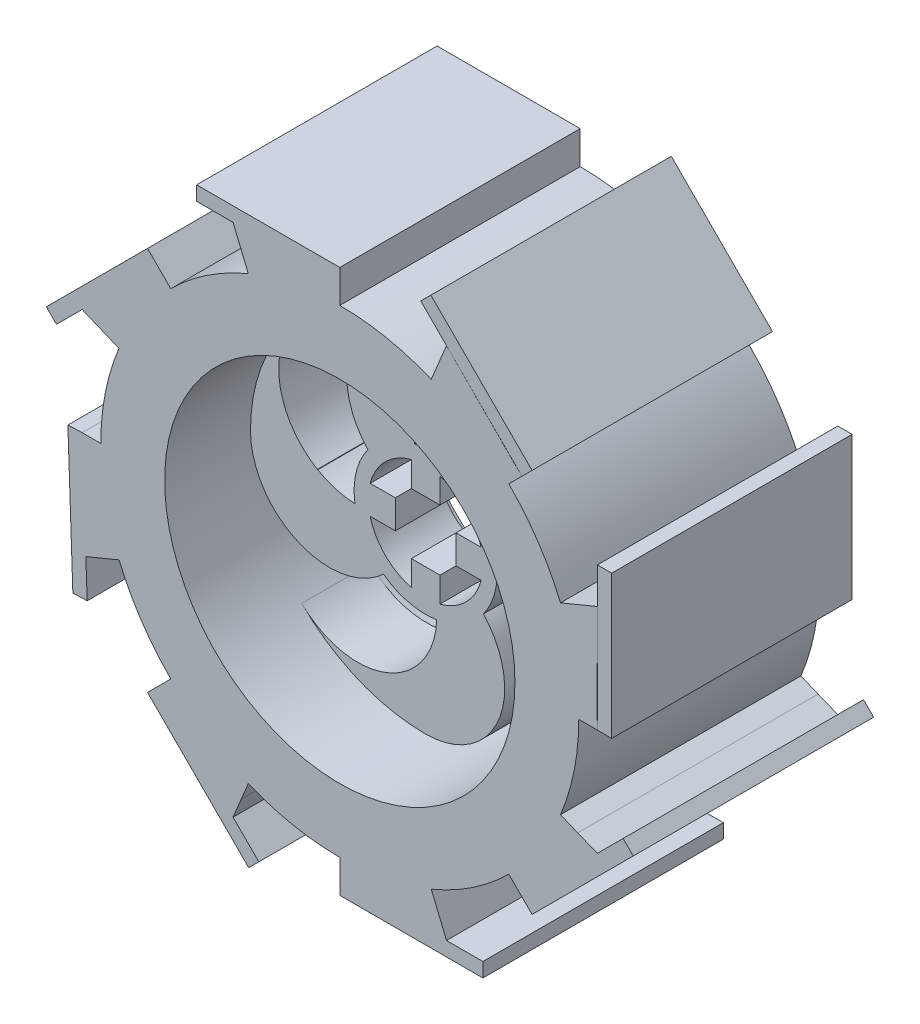
SolidWorks part; units mm, degrees
ref_plane "Front Plane" through (0, 0, 0) normal (0, 0, 1) x (1, 0, 0)
ref_plane "Top Plane" through (0, 0, 0) normal (0, 1, 0) x (1, 0, 0)
ref_plane "Right Plane" through (0, 0, 0) normal (1, 0, 0) x (0, 0, -1)
sketch "Sketch1" plane through (0, 0, 0) normal (0, 0, 1) x (1, 0, 0)
  line L0 (0, 83.5) -> (0, -83.5)
  line L1 (-83.5, 0) -> (83.5, 0)
  line L2 (0, 0) -> (59.0434, 59.0434)
  line L3 (0, 0) -> (-59.0434, 59.0434)
  line L4 (0, 0) -> (-59.0434, -59.0434)
  line L5 (0, 0) -> (63.6396, -63.6396)
  line L6 (0, 0) -> (-31.9541, 77.1439)
  line L7 (0, 0) -> (31.9541, -77.1439)
  line L8 (0, 0) -> (59.0434, -59.0434)
  line L9 (0, 0) -> (34.4523, 83.1447)
  line L10 (-31.9541, -77.1439) -> (0, 0)
  line L11 (-77.1439, -31.9541) -> (0, 0)
  line L12 (0, 0) -> (77.1439, 31.9541)
  line L13 (0, 0) -> (31.9541, 77.1439)
  line L14 (0, 0) -> (-77.1439, 31.9541)
  line L15 (-77.1439, 31.9541) -> (77.1439, -31.9541)
  line L16 (0, 0) -> (0, 90)
  line L17 (0, 0) -> (63.6396, 63.6396)
  line L18 (0, 0) -> (-34.4523, 83.1447)
  line L19 (0, 0) -> (-63.6396, 63.6396)
  line L20 (0, 0) -> (-83.5, 34.5496)
  line L21 (0, 0) -> (-90, 0)
  line L22 (0, 0) -> (-83.111, -34.5335)
  line L23 (0, 0) -> (-83.111, -34.5335)
  line L24 (0, 0) -> (-63.6396, -63.6396)
  line L25 (0, 0) -> (-34.4523, -83.1447)
  line L26 (0, 0) -> (0, -90)
  line L27 (0, 0) -> (34.4523, -83.1447)
  line L28 (0, 0) -> (83.111, -34.5335)
  line L29 (0, 0) -> (90, 0)
  line L30 (0, 0) -> (83.1043, 34.5496)
  circle A0 centre (0, 0) radius 90
  circle A1 centre (0, 0) radius 1.95
  circle A2 centre (0, 0) radius 83.5
  dimension "D1" = 180
  dimension "D2" = 3.9
  dimension "D3" = 167
  dimension "D5" = 45
  dimension "D6" = 22.5
  dimension "D7" = 22.5
extrude "Boss-Extrude1" add sketch "Sketch1" along normal blind 84 contours A2 L16 A0 L18 | A2 L17 A0 L9 | A2 L29 A0 L30 | A2 L5 A0 L28 | A2 L26 A0 L27 | A2 L24 A0 L25 | A2 L21 A0 L22 | A2 L19 A0 L20 | A2 region at (-16.8288, 84.5756, 0) region at (47.9139, 71.6981, 0) region at (-71.7092, 47.8948, 0) region at (16.8288, -84.5756, 0) region at (84.5625, 16.8777, 0) region at (-84.5646, -16.8696, 0) region at (-47.9139, -71.6981, 0) region at (71.677, -47.9505, 0)
sketch "Sketch13" plane through (0, 0, 84) normal (0, 0, 1) x (1, 0, 0)
  line L0 (90, 0) -> (90, 50)
  line L21 (63.6396, 63.6396) -> (28.2843, 98.9949)
  line L22 (0, 90) -> (-50, 90)
  line L23 (-63.6396, 63.6396) -> (-98.9949, 28.2843)
  line L24 (-90, 0) -> (-88.2609, -50)
  line L25 (-63.6396, -63.6396) -> (-28.2843, -98.9949)
  line L26 (0, -90) -> (50, -90)
  line L27 (63.6396, -63.6396) -> (98.9949, -28.2843)
  line L28 (28.2843, 98.9949) -> (63.6396, 63.6396)
  line L29 (28.2843, 98.9949) -> (31.8198, 102.5305)
  line L30 (63.6396, 63.6396) -> (67.1751, 67.1751)
  line L31 (31.8198, 102.5305) -> (67.1751, 67.1751)
  line L32 (0, 90) -> (-50, 90)
  line L33 (0, 90) -> (0, 95)
  line L34 (-50, 90) -> (-50, 95)
  line L35 (0, 95) -> (-50, 95)
  line L36 (-98.9949, 28.2843) -> (-63.6396, 63.6396)
  line L37 (-98.9949, 28.2843) -> (-102.5305, 31.8198)
  line L38 (-63.6396, 63.6396) -> (-67.1751, 67.1751)
  line L39 (-102.5305, 31.8198) -> (-67.1751, 67.1751)
  line L40 (-90, 0) -> (-88.2609, -50)
  line L41 (-90, 0) -> (-95, -0.1739)
  line L42 (-88.2609, -50) -> (-93.2609, -50.1739)
  line L43 (-95, -0.1739) -> (-93.2609, -50.1739)
  line L44 (-63.6396, -63.6396) -> (-28.2843, -98.9949)
  line L45 (-63.6396, -63.6396) -> (-67.1751, -67.1751)
  line L46 (-28.2843, -98.9949) -> (-31.8198, -102.5305)
  line L47 (-67.1751, -67.1751) -> (-31.8198, -102.5305)
  line L48 (0, -90) -> (50, -90)
  line L49 (0, -90) -> (0, -95)
  line L50 (50, -90) -> (50, -95)
  line L51 (0, -95) -> (50, -95)
  line L52 (63.6396, -63.6396) -> (98.9949, -28.2843)
  line L53 (63.6396, -63.6396) -> (67.1751, -67.1751)
  line L54 (98.9949, -28.2843) -> (102.5305, -31.8198)
  line L55 (67.1751, -67.1751) -> (102.5305, -31.8198)
  line L56 (90, 0) -> (90, 50)
  line L57 (90, 0) -> (95, 0)
  line L58 (90, 50) -> (95, 50)
  line L59 (95, 0) -> (95, 50)
  arc A1 (-90, 0) -> (-83.111, -34.5335) centre (0, 0) ccw construction
  arc M26 (-90, 0) -> (-83.111, -34.5335) centre (0, 0) ccw
  dimension "D1" = 50
  dimension "D2" = 50
  dimension "D3" = 50
  dimension "D4" = 50
  dimension "D5" = 50
  dimension "D6" = 50
  dimension "D7" = 50
  dimension "D8" = 50
  dimension "D9" = 5
  dimension "D10" = 5
  dimension "D11" = 5
  dimension "D12" = 5
  dimension "D13" = 5
  dimension "D14" = 5
  dimension "D15" = 5
  dimension "D16" = 5
extrude "Cleats" add sketch "Sketch13" against normal blind 84 contours L39 L37 L23 L38 | L41 L43 L42 L24 M26 | L45 L47 L46 L25 | L49 L51 L50 L26 | L53 L55 L54 L27 | L57 L59 L58 L0 | L31 L29 L21 L30 | L33 L35 L34 L22 region at (92.5, 25, 84) region at (47.7297, 83.085, 84) region at (-25, 92.5, 84) region at (-83.085, 47.7297, 84) region at (-91.632, -25.1069, 84) region at (-47.7297, -83.085, 84) region at (25, -92.5, 84) region at (83.085, -47.7297, 84)
sketch "Sketch14" plane through (0, 0, 0) normal (0, 0, -1) x (-1, 0, 0)
  line L1 (-63.6396, 63.6396) -> (-28.2843, 98.9949) construction
  line L2 (-37.2889, 89.9904) -> (-61.0783, 66.1017)
  line L3 (-61.0783, 66.1017) -> (-34.4523, 83.1447)
  line L5 (0, 90) -> (50, 90) construction
  line L6 (37.2928, 90) -> (0, 90)
  line L7 (0, 90) -> (34.4523, 83.1447)
  line L8 (63.6396, 63.6396) -> (82.9874, 34.8294)
  line L10 (63.6396, 63.6396) -> (98.9949, 28.2843) construction
  line L11 (88.6482, 38.631) -> (63.6396, 63.6396)
  line L12 (83.111, -34.5335) -> (88.7181, -36.8569)
  line L13 (89.7825, -6.253) -> (88.2609, -50) construction
  line L14 (88.7181, -36.8569) -> (90, 0)
  line L15 (90, 0) -> (83.111, -34.5335)
  line L16 (83.1623, 34.4098) -> (90.0284, 37.2508)
  line L18 (63.6396, -63.6396) -> (28.2843, -98.9949) construction
  line L19 (39.2934, -87.9858) -> (63.6396, -63.6396)
  line L20 (63.6396, -63.6396) -> (34.4523, -83.1447)
  line L21 (0, -90) -> (-34.4523, -83.1447)
  line L23 (0, -90) -> (-50, -90) construction
  line L24 (-34.4523, -90) -> (0, -90)
  line L25 (-63.6396, -63.6396) -> (-83.111, -34.5335)
  line L27 (-63.6396, -63.6396) -> (-98.9949, -28.2843) construction
  line L28 (-87.9283, -39.3509) -> (-63.6396, -63.6396)
  line L29 (-90, 0) -> (-83.1043, 34.5496)
  line L30 (90.0284, 37.2508) -> (63.6396, 63.6396)
  line L31 (-90, 0) -> (-90, 50) construction
  line L32 (-90, 34.5496) -> (-89.8887, 0.5574)
  line L35 (-90, 34.5496) -> (-90, 37.4164)
  line L37 (-90, -37.2792) -> (-87.9283, -39.3509)
  line L38 (88.6482, 38.631) -> (90.0284, 37.2508)
  line L39 (37.2928, -89.9864) -> (39.2934, -87.9858)
  line L40 (-37.2928, -90) -> (-34.4523, -90)
  line L43 (37.2928, -89.9864) -> (63.6396, -63.6396)
  line L44 (-37.2928, -90) -> (0, -90)
  line L45 (-90, -37.2792) -> (-63.6396, -63.6396)
  line L46 (-83.111, -34.5335) -> (-90, -37.2792)
  line L47 (-83.1043, 34.5496) -> (-90, 37.4164)
  line L48 (-34.4523, 83.1447) -> (-37.2889, 89.9904)
  line L49 (34.4523, 83.1447) -> (37.3476, 90.132)
  line L50 (34.4523, -83.1447) -> (37.2928, -89.9864)
  line L51 (-34.4523, -83.1447) -> (-37.2928, -90)
  line L52 (-83.111, -34.5335) -> (-90, -37.2792)
  arc M4 (-34.4523, 83.1447) -> (-63.6396, 63.6396) centre (0, 0) ccw
  arc M8 (-83.1043, 34.5496) -> (-90, 0) centre (0, 0) ccw
  arc M12 (-83.111, -34.5335) -> (-63.6396, -63.6396) centre (0, 0) ccw
  arc M16 (-34.4523, -83.1447) -> (0, -90) centre (0, 0) ccw
  arc M20 (34.4523, -83.1447) -> (63.6396, -63.6396) centre (0, 0) ccw
  arc M24 (83.111, -34.5335) -> (89.7825, -6.253) centre (0, 0) ccw
  line M25 (89.7825, -6.253) -> (88.2609, -50)
  arc M32 (83.1623, 34.4098) -> (63.6396, 63.6396) centre (0, 0) ccw
  arc M36 (34.4523, 83.1447) -> (0, 90) centre (0, 0) ccw
extrude "cleats_2" add sketch "Sketch14" against normal blind 84 contours L47 L35 L32 M8 | L48 L2 M4 | L49 L6 M36 | L16 L30 L11 M32 | L12 M24 M25 | L50 L39 L19 M20 | L51 L40 L24 M16 | L46 L37 L28 M12 region at (42.967, 81.3466, 0) region at (-26.9658, 87.9305, 0) region at (-81.2548, 43.094, 0) region at (-87.31, -27.8014, 0) region at (-43.1249, -81.2314, 0) region at (26.9658, -87.9305, 0) region at (81.2206, -43.1487, 0) region at (87.8792, 27.3093, 0)
sketch "Sketch15" plane through (0, 0, 84) normal (0, 0, 1) x (1, 0, 0)
  circle A0 centre (0, 0) radius 61.2
  circle A1 centre (0, 0) radius 20
  dimension "D1" = 122.4
  dimension "D2" = 40
extrude "Middle_cut" cut sketch "Sketch15" against normal blind 84
sketch "Sketch17" plane through (0, 0, 0) normal (0, 0, -1) x (-1, 0, 0)
  line L0 (0, 0) -> (0, 95)
  line L1 (0, 0) -> (67.1751, 67.1751)
  line L2 (0, 0) -> (95, -0.1739)
  line L3 (0, 0) -> (67.1751, -67.1751)
  line L4 (0, 0) -> (0, -95)
  line L5 (0, 0) -> (-67.1751, -67.1751)
  line L6 (0, 0) -> (-95, 0)
  line L7 (0, 0) -> (-67.1751, 67.1751)
  circle A0 centre (0, 0) radius 61.2
  circle A1 centre (0, 33.5876) radius 27.6124
  circle A3 centre (23.75, 23.75) radius 27.6124
  circle A4 centre (33.5876, 0) radius 27.6126
  circle A5 centre (23.75, -23.75) radius 27.6124
  circle A6 centre (0, -33.5876) radius 27.6124
  circle A7 centre (-23.75, -23.75) radius 27.6124
  circle A8 centre (-33.5876, 0) radius 27.6124
  circle A9 centre (-23.75, 23.75) radius 27.6124
  circle M2 centre (0, 0) radius 20
extrude "Boss-Extrude13" add sketch "Sketch17" against normal blind 84 contours A8 A9 A7 A1 M2 | A9 A8 L6 | L6 A8 A7 | L7 A1 M2 | A8 L7 M2 | A8 A6 A7 A5 M2 | A7 A6 L4 | L4 A6 A5 | A6 L5 M2 | L5 A8 M2 | A5 A4 L2 | A6 L3 A4 A5 L2 A3 M2 | L3 A6 M2 | A4 A6 L3 M2 | A5 L2 A0 A4 A3 | A9 A4 A1 A3 M2 | A1 A4 L1 M2 | A1 L1 M2 | A3 A1 L0 | A9 L0 A1 | A9 A1 A0 | A4 A0 A3 | A6 A0 A5 | A8 A0 A7 region at (-14.3631, 34.6756, 0) region at (-17.9448, 20.286, 0) region at (-20.286, 17.9448, 0) region at (-20.286, -17.9448, 0) region at (-17.9448, -20.286, 0) region at (-34.6755, -14.3633, 0) region at (14.3631, -34.6756, 0) region at (17.9448, -20.286, 0) region at (20.286, -17.9448, 0) region at (34.6756, 14.3631, 0) region at (20.286, 17.9448, 0) region at (17.9448, 20.286, 0) region at (7.145, 52.2917, 0) region at (-7.145, 52.2917, 0) region at (-7.145, -52.2917, 0) region at (7.145, -52.2917, 0) region at (52.2917, -7.145, 0) region at (52.2917, 7.145, 0) region at (22.5931, 54.5445, 0) region at (-54.5444, 22.5935, 0) region at (-52.2756, 7.0817, 0) region at (-22.5931, -54.5445, 0) region at (-52.3082, -7.2086, 0) region at (54.5445, -22.5931, 0)
sketch "Sketch18" plane through (0, 0, 84) normal (0, 0, 1) x (1, 0, 0)
  circle A0 centre (0, 0) radius 61.2
extrude "Wheel_cut1" cut sketch "Sketch18" against normal blind 30
sketch "Sketch19" plane through (0, 0, 0) normal (0, 0, -1) x (-1, 0, 0)
  circle A0 centre (0, 0) radius 61.2
extrude "wheel_cut2" cut sketch "Sketch19" against normal blind 30
sketch "Sketch20" plane through (0, 0, 30) normal (0, 0, -1) x (-1, 0, 0)
  circle A0 centre (0, 0) radius 25
  dimension "D1" = 50
extrude "Boss-Extrude14" add sketch "Sketch20" against normal blind 24
sketch "Sketch21" plane through (0, 0, 30) normal (0, 0, -1) x (-1, 0, 0)
  line L0 (0, 0) -> (0, 20)
  line L1 (0, 0) -> (-20, 0)
  line L2 (0, 0) -> (20, 0)
  line L3 (0, 0) -> (0, -20)
  line L5 (-5, -19.3649) -> (-5, 19.3649)
  line L6 (5, -19.3649) -> (5, 19.3649)
  line L7 (-19.3649, 5) -> (19.3649, 5)
  line L8 (-19.3649, -5) -> (19.3649, -5)
  line L9 (-5, 10.6) -> (5, 10.6)
  line L10 (-10.6, 5) -> (-10.6, -5)
  line L11 (-5, -10.6) -> (5, -10.6)
  line L12 (10.6, -5) -> (10.6, 5)
  circle A0 centre (0, 0) radius 20
  dimension "D1" = 5
  dimension "D2" = 40
  dimension "D3" = 5
  dimension "D4" = 5
  dimension "D5" = 5
  dimension "D6" = 9.4
  dimension "D7" = 9.4
  dimension "D8" = 9.4
  dimension "D9" = 9.4
extrude "Cut-Extrude4" cut sketch "Sketch21" against normal blind 84 contours L5 A0 L7 | L9 L5 L7 L0 | L9 L0 L7 L6 | L7 A0 L6 | L2 L12 L7 L6 | L8 L12 L2 L6 | L6 A0 L8 | L7 L0 L2 L6 | L7 L5 L1 L0 | L5 L8 L3 L1 | L3 L8 L6 L2 | L8 A0 L5 | L1 L10 L8 L5 | L7 L10 L1 L5 | L5 L11 L3 L8 | L3 L11 L6 L8 region at (2.5, 2.5, 30) region at (2.5, -2.5, 30) region at (-2.5, 2.5, 30) region at (-2.5, -2.5, 30) region at (2.5, 7.8, 30) region at (-2.5, 7.8, 30) region at (7.8, -2.5, 30) region at (7.8, 2.5, 30) region at (-7.8, 2.5, 30) region at (-7.8, -2.5, 30) region at (-2.5, -7.8, 30) region at (2.5, -7.8, 30) region at (10.6465, 10.6465, 30) region at (-10.6465, 10.6465, 30) region at (10.6465, -10.6465, 30) region at (-10.6465, -10.6465, 30)
